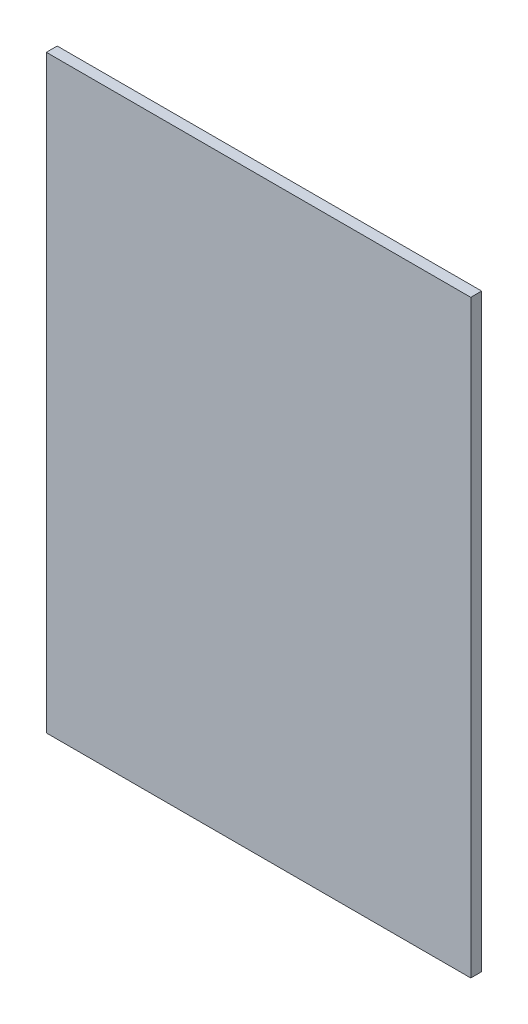
SolidWorks part; units mm, degrees
ref_plane "Front Plane" through (0, 0, 0) normal (0, 0, 1) x (1, 0, 0)
ref_plane "Top Plane" through (0, 0, 0) normal (0, 1, 0) x (1, 0, 0)
ref_plane "Right Plane" through (0, 0, 0) normal (1, 0, 0) x (0, 0, -1)
sketch "Sketch1" plane through (0, 0, 0) normal (0, 0, 1) x (1, 0, 0)
  line L1 (0, 0) -> (1170, 0)
  line L2 (0, 0) -> (0, 1625)
  line L3 (0, 1625) -> (1170, 1625)
  line L4 (1170, 0) -> (1170, 1625)
  dimension "D1" = 1170
  dimension "D2" = 1625
extrude "Boss-Extrude1" add sketch "Sketch1" along normal blind 30
